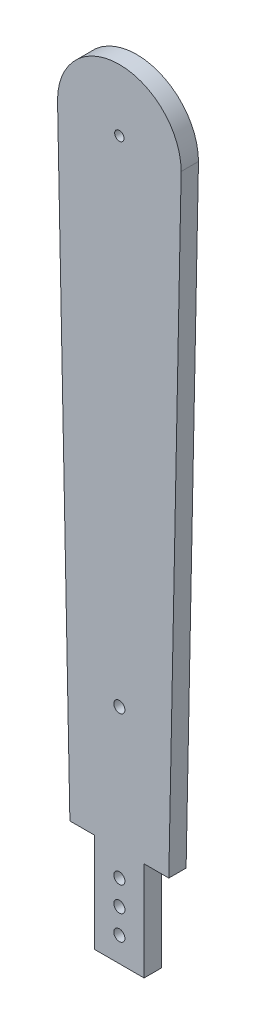
SolidWorks part; units mm, degrees
other "Markup1"
sketch "Sketch21" plane through (-25, -390, 7) normal (-0.035, -0.0156, 0.9993) x (0.9974, 0.0629, 0.0359)
other "Markup2"
sketch "Sketch22" plane through (-25, -390, 7) normal (-0.218, -0.9748, 0.047) x (0.9498, -0.2008, 0.2398)
ref_plane "Front Plane" through (0, 0, 0) normal (0, 0, 1) x (1, 0, 0)
ref_plane "Top Plane" through (0, 0, 0) normal (0, 1, 0) x (1, 0, 0)
ref_plane "Right Plane" through (0, 0, 0) normal (1, 0, 0) x (0, 0, -1)
sketch "Sketch7" plane through (0, 0, 0) normal (0, 0, 1) x (1, 0, 0)
  line L0 (-25, 0) -> (-20, -250)
  line L1 (-20, -250) -> (20, -250)
  line L2 (25, 0) -> (20, -250)
  arc A0 (25, 0) -> (-25, 0) centre (0, 0) ccw
  arc A1 (-24.98, -0.9996) -> (24.98, -0.9996) centre (0, 0) ccw
  point P9 (0, -250)
  dimension "D2" = 50
  dimension "D1" = 250
  dimension "D3" = 40
extrude "Boss-Extrude3" add sketch "Sketch7" along normal mid plane 7 contours L0 A1 L2 A0 | A1 L0 L1 L2 region at (0, 0, 0) region at (0, -130.8644, 0)
ref_plane "Plane2" through (0, 0, 0) normal (0, 0, 1) x (1, 0, 0)
sketch "Sketch14" plane through (0, -250, 0) normal (0, -1, 0) x (1, 0, 0)
  line L1 (-10, -3.5) -> (10, -3.5)
  line L2 (-10, -3.5) -> (-10, 3.5)
  line L3 (-10, 3.5) -> (10, 3.5)
  line L4 (10, -3.5) -> (10, 3.5)
  line L5 (-10, -3.5) -> (10, 3.5) construction
  line L6 (-10, 3.5) -> (10, -3.5) construction
  point P0 (0, 0)
  dimension "D1" = 20
  dimension "D2" = 7
sketch "Sketch17" plane through (0, 0, 3.5) normal (0, 0, 1) x (1, 0, 0)
  circle A0 centre (0, 0) radius 1.9
  dimension "D1" = 3.8
sketch "Sketch18" plane through (0, 0, 3.5) normal (0, 0, 1) x (1, 0, 0)
  circle A0 centre (0, -200) radius 2.25
  dimension "D1" = 4.5
  dimension "D2" = 200
extrude "Cut-Extrude10" cut sketch "Sketch18" against normal blind 14
extrude "Cut-Extrude13" cut sketch "Sketch17" against normal mid plane 48
extrude "Boss-Extrude4" add sketch "Sketch14" along normal blind 40
sketch "Sketch23" plane through (0, 0, 3.5) normal (0, 0, 1) x (1, 0, 0)
  line L0 (0, -200) -> (0, -290)
  line L1 (10, -290) -> (-10, -290) construction
  line L2 (-20, -250) -> (-10, -250) construction
  circle A0 centre (0, -260) radius 2.25
  circle A1 centre (0, -270) radius 2.25
  circle A2 centre (0, -280) radius 2.25
  dimension "D1" = 4.5
  dimension "D3" = 10
  dimension "D2" = 3
extrude "Cut-Extrude15" cut sketch "Sketch23" against normal blind 7 contours L0 A0 | L0 A0 | L0 A1 | L0 A1 | L0 A2 | L0 A2 region at (0.9549, -260, 3.5) region at (0.9549, -280, 3.5) region at (-0.9549, -280, 3.5) region at (0.9549, -270, 3.5) region at (-0.9549, -270, 3.5) region at (-0.9549, -260, 3.5)
